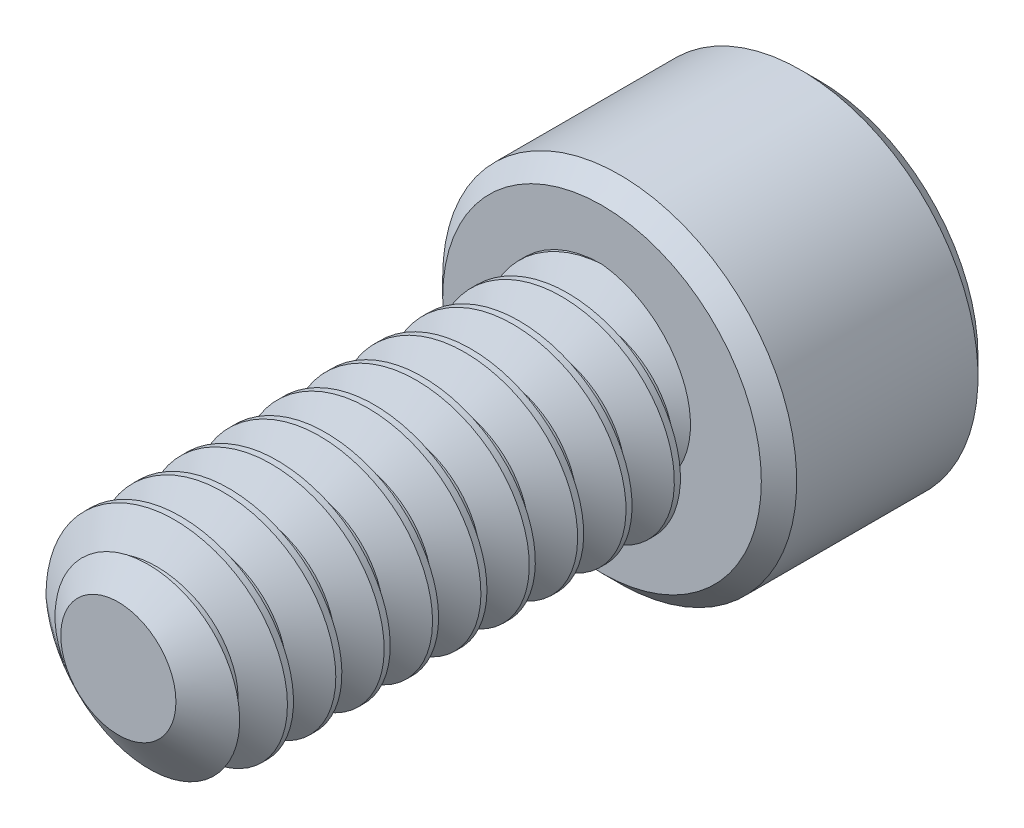
SolidWorks part; units mm, degrees
material "Alloy Steel"
ref_plane "Front Plane" through (0, 0, 0) normal (0, 0, 1) x (1, 0, 0)
ref_plane "Top Plane" through (0, 0, 0) normal (0, 1, 0) x (1, 0, 0)
ref_plane "Right Plane" through (0, 0, 0) normal (1, 0, 0) x (0, 0, -1)
sketch "Sketch1" plane through (0, 0, 0) normal (0, 0, 1) x (1, 0, 0)
  circle A0 centre (0, 0) radius 1.4224
  dimension "OD" = 2.8448
extrude "Extrude1" add sketch "Sketch1" against normal blind 6.35
sketch "Sketch2" plane through (0, 0, 0) normal (0, 0, 1) x (1, 0, 0)
  circle A0 centre (0, 0) radius 1.4224 construction
  circle A1 centre (0, 0) radius 1.4224
curve "Helix/Spiral1" pitch 0.635 height 6.985 radius 1.4224 centre (0, 0, 0) axis (0, 0, -1) start towards (0, 1, 0) parameters "pitch"=0.635
sketch "Sketch3" plane through (0, 0, 0) normal (1, 0, 0) x (0, 0, -1)
  line L0 (-0.5556, 1.4224) -> (-0.3175, 1.01)
  line L1 (-0.3175, 1.01) -> (-0.2381, 1.01)
  line L2 (-0.2381, 1.01) -> (0, 1.4224)
  line L3 (-0.5556, 1.4224) -> (0, 1.4224)
  line L4 (-0.2778, 1.4224) -> (-0.2778, 1.01) construction
  line L5 (-0.4366, 1.2162) -> (-0.1191, 1.2162) construction
  line L6 (0, 1.4224) -> (0, -1.4224) construction
  dimension "D1" = 0.0794
  dimension "D2" = 0.3175
  dimension "D3" = 60
sweep "Cut-Sweep1" cut profiles "Sketch3" path "Helix/Spiral1"
sketch "Sketch4" plane through (0, 0, 0) normal (1, 0, 0) x (0, 0, -1)
  line L0 (0.4666, 1.4224) -> (0, 0.756)
  line L1 (0, 0.756) -> (0, 1.4224)
  line L2 (0.4666, 1.4224) -> (0, 1.4224)
  line L3 (-0.5556, 1.4224) -> (0, 1.4224) construction
  line L4 (0, 0) -> (7.0209, 0) construction
  dimension "D1" = 55
  dimension "D2" = 0.254
revolve "Cut-Revolve1" cut sketch "Sketch4" angle 360 about L4
sketch "Sketch5" plane through (0, 0, 0) normal (1, 0, 0) x (0, 0, -1)
  line L0 (6.35, -1.0232) -> (6.35, 1.0149) construction
  line L1 (6.35, 1.5494) -> (38.1885, 1.5494)
  line L2 (6.35, 1.5494) -> (6.35, 0)
  line L3 (6.35, 0) -> (38.1, 0)
  line L4 (38.1, 1.2192) -> (38.1, 0)
  line L5 (38.1885, 1.5494) -> (38.1, 1.2192)
  line L6 (0, 0) -> (9.9695, 0) construction
  point P3 (38.1, 1.5494)
  point P10 (38.1, 1.5494)
  dimension "D1" = 0.3302
  dimension "Thread min" = 38.1
  dimension "D2" = 0.127
  dimension "D3" = 15
revolve "partially thread" [suppressed] add sketch "Sketch5" angle 360 about L6
sketch "Sketch6" plane through (0, 0, -6.35) normal (0, 0, -1) x (-1, 0, 0)
  circle A0 centre (0, 0) radius 2.3241
  dimension "head dia" = 4.6482
extrude "Extrude2" add sketch "Sketch6" along normal blind 2.8448
sketch "Sketch7" plane through (0, 0, -9.1948) normal (0, 0, -1) x (-1, 0, 0)
  line L1 (0, 1.3748) -> (-1.1906, 0.6874)
  line L2 (-1.1906, 0.6874) -> (-1.1906, -0.6874)
  line L3 (-1.1906, -0.6874) -> (0, -1.3748)
  line L4 (0, -1.3748) -> (1.1906, -0.6874)
  line L5 (1.1906, -0.6874) -> (1.1906, 0.6874)
  line L6 (1.1906, 0.6874) -> (0, 1.3748)
  circle A0 centre (0, 0) radius 1.1906 construction
  dimension "hex dia" = 2.3813
extrude "Cut-Extrude1" cut sketch "Sketch7" against normal blind 1.7859
sketch "Sketch8" plane through (0, 0, -9.1948) normal (0, 0, -1) x (-1, 0, 0)
  circle A0 centre (0, 0) radius 1.3748
extrude "Cut-Extrude2" cut sketch "Sketch8" against normal through all draft 45
chamfer "Chamfer1" distance 0.2324 angle 45 2 edges at (-2.3241, 0, -9.1948) (-2.3241, 0, -6.35)
sketch "Sketch9" plane through (0, 0, 0) normal (1, 0, 0) x (0, 0, -1)
  line L0 (0, 1.4224) -> (0, -1.4224) construction
  line L1 (6.6675, 1.4224) -> (6.6675, -1.4224) construction
  dimension "D1" = 6.6675
equation "\"D3@Helix/Spiral1\" = \"screw length@Extrude1\"+\"pitch@Helix/Spiral1\""
equation "\"D1@Sketch3\" = \"pitch@Helix/Spiral1\"*.125"
equation "\"D2@Sketch3\" = \"pitch@Helix/Spiral1\"*.5"
equation "\"D1@Cut-Extrude1\" = \"hex dia@Sketch7\"*.75"
equation "\"D1@Chamfer1\" = \"head dia@Sketch6\"*.05"
equation "\"D1@Sketch9\" = \"pitch@Helix/Spiral1\"*10.5"
